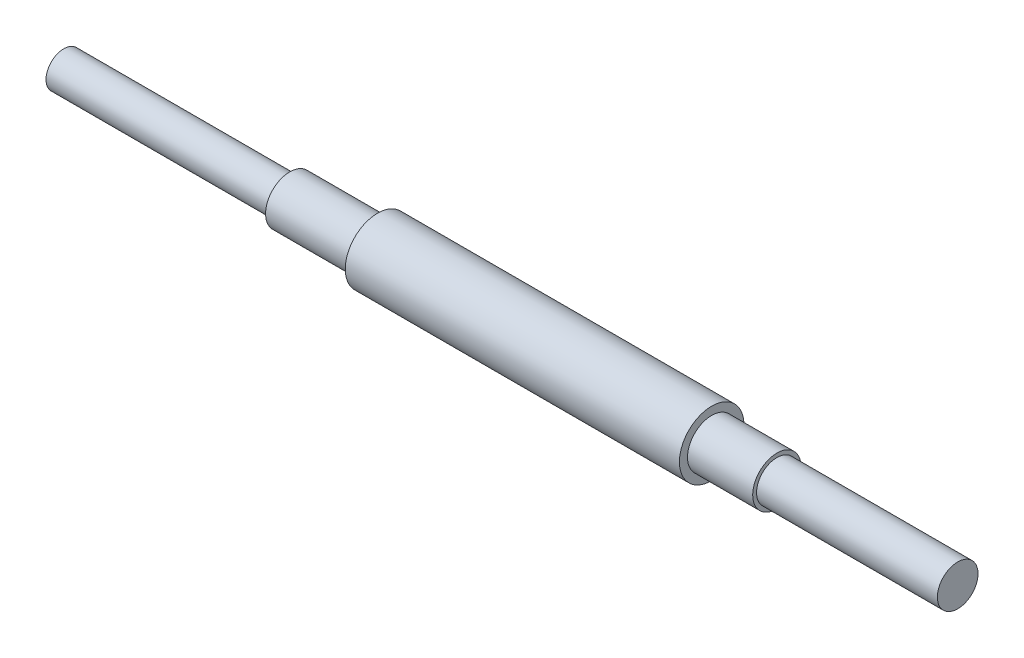
SolidWorks part; units mm, degrees
ref_plane "Front Plane" through (0, 0, 0) normal (0, 0, 1) x (1, 0, 0)
ref_plane "Top Plane" through (0, 0, 0) normal (0, 1, 0) x (1, 0, 0)
ref_plane "Right Plane" through (0, 0, 0) normal (1, 0, 0) x (0, 0, -1)
sketch "Sketch1" plane through (0, 0, 0) normal (0, 1, 0) x (1, 0, 0)
  line L0 (-78.6306, 0) -> (97.1762, 0) construction
  line L1 (-78.6306, 0) -> (-78.6306, 3.5)
  line L2 (-78.6306, 3.5) -> (-34.1806, 3.5)
  line L3 (-34.1806, 3.5) -> (-34.1806, 4.7625)
  line L4 (-34.1806, 4.7625) -> (-16.9251, 4.7625)
  line L5 (-16.9251, 4.7625) -> (-16.9251, 6.35)
  line L6 (-16.9251, 6.35) -> (48.7948, 6.35)
  line L7 (48.7948, 6.35) -> (48.7948, 4.7625)
  line L8 (48.7948, 4.7625) -> (61.6162, 4.7625)
  line L9 (61.6162, 4.7625) -> (61.6162, 3.9992)
  line L10 (61.6162, 3.9992) -> (97.1762, 3.9992)
  line L11 (97.1762, 3.9992) -> (97.1762, 0)
  line L12 (-78.6306, 0) -> (97.1762, 0)
  line L13 (-97.9506, 0) -> (194.5593, 0) construction
  dimension "D1" = 7
  dimension "D2" = 9.525
  dimension "D3" = 9.525
  dimension "D4" = 7.9985
  dimension "D5" = 44.45
  dimension "D6" = 17.2554
  dimension "D7" = 12.8214
  dimension "D8" = 35.56
  dimension "D9" = 65.72
  dimension "D10" = 6.35
revolve "Revolve1" add sketch "Sketch1" angle 360 about L13
